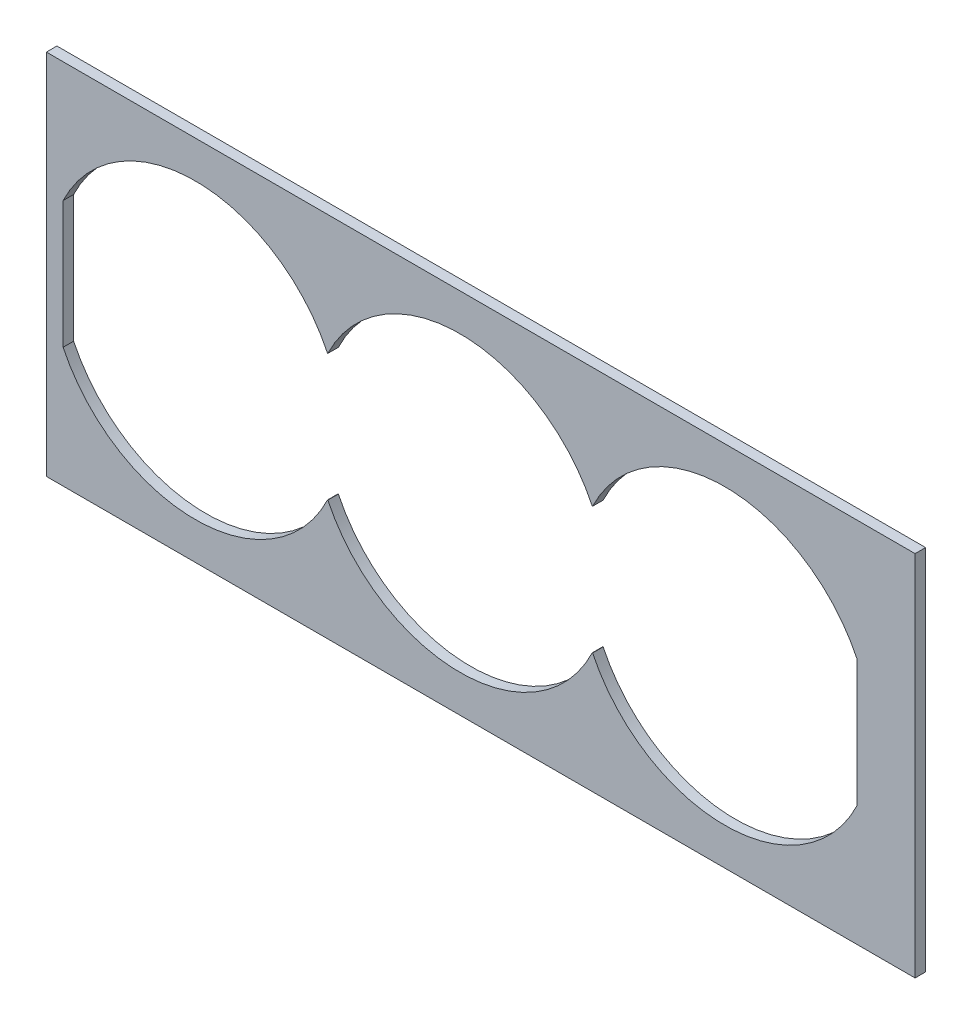
SolidWorks part; units mm, degrees
material "Silicon"
ref_plane "Front" through (0, 0, 0) normal (0, 0, 1) x (1, 0, 0)
ref_plane "Top" through (0, 0, 0) normal (0, 1, 0) x (1, 0, 0)
ref_plane "Right" through (0, 0, 0) normal (1, 0, 0) x (0, 0, -1)
sketch "Sketch4" plane through (0, 0, 0) normal (0, 0, 1) x (1, 0, 0)
  line L0 (165.1, 0) -> (165.1, 139.7) construction
  line L1 (207.493, 93.9963) -> (207.493, 45.7037) construction
  line L2 (0, 0) -> (330.2, 0)
  line L3 (165.1, 69.85) -> (56.604, 69.85) construction
  line L4 (6.35, 93.9963) -> (6.35, 45.7037)
  line L5 (106.858, 93.9963) -> (106.858, 45.7037) construction
  line L6 (0, 0) -> (0, 139.7)
  line L7 (0, 139.7) -> (330.2, 139.7)
  line L8 (330.2, 0) -> (330.2, 139.7)
  line L9 (106.985, 93.9963) -> (106.985, 45.7037) construction
  line L10 (308.128, 93.9963) -> (308.128, 45.7037)
  line L11 (207.62, 93.9963) -> (207.62, 45.7037) construction
  line L12 (106.858, 93.9963) -> (106.985, 93.9963)
  line L13 (207.493, 93.9963) -> (207.62, 93.9963)
  line L14 (207.62, 45.7037) -> (207.493, 45.7037)
  line L15 (106.985, 45.7037) -> (106.858, 45.7037)
  arc A0 (6.35, 45.7037) -> (106.858, 45.7037) centre (56.604, 69.85) ccw
  arc A1 (106.858, 93.9963) -> (6.35, 93.9963) centre (56.604, 69.85) ccw
  arc A2 (106.985, 45.7037) -> (207.493, 45.7037) centre (157.239, 69.85) ccw
  arc A3 (207.493, 93.9963) -> (106.985, 93.9963) centre (157.239, 69.85) ccw
  arc A4 (207.62, 45.7037) -> (308.128, 45.7037) centre (257.874, 69.85) ccw
  arc A5 (308.128, 93.9963) -> (207.62, 93.9963) centre (257.874, 69.85) ccw
  point P8 (165.1, 69.85)
  dimension "D2" = 111.508
  dimension "D1" = 100.508
  dimension "D3" = 139.7
  dimension "D4" = 330.2
  dimension "D6" = 6.35
  dimension "D7" = 0.127
  dimension "D5" = 3
extrude "DIMENSIONS CONTROL OPTICS LOCATION" add sketch "Sketch4" along normal blind 4
